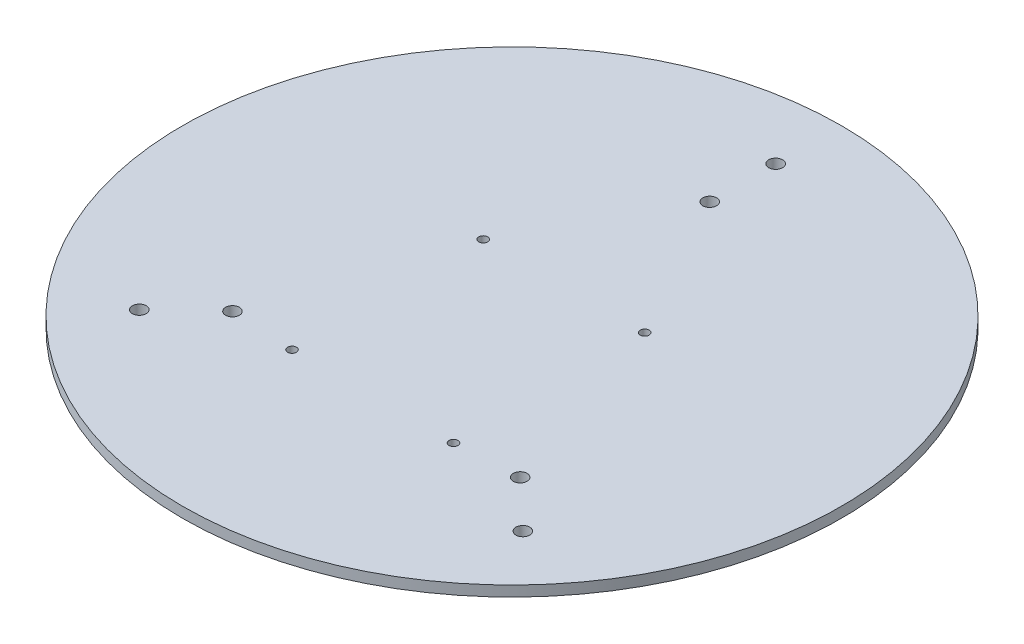
SolidWorks part; units mm, degrees
ref_plane "Front Plane" through (0, 0, 0) normal (0, 0, 1) x (1, 0, 0)
ref_plane "Top Plane" through (0, 0, 0) normal (0, 1, 0) x (1, 0, 0)
ref_plane "Right Plane" through (0, 0, 0) normal (1, 0, 0) x (0, 0, -1)
sketch "Sketch1" plane through (0, 0, 0) normal (0, 1, 0) x (1, 0, 0)
  line L0 (0, 100) -> (0, -100) construction
  line L1 (-24.5, 42.25) -> (24.5, 42.25) construction
  line L2 (-24.5, 42.25) -> (-24.5, -42.25) construction
  line L3 (-24.5, -42.25) -> (24.5, -42.25) construction
  line L4 (24.5, 42.25) -> (24.5, -42.25) construction
  line L5 (-24.5, 42.25) -> (24.5, -42.25) construction
  line L6 (-24.5, -42.25) -> (24.5, 42.25) construction
  line L7 (-24.5, -42.25) -> (24.5, -42.25) construction
  line L8 (-24.5, -42.25) -> (-24.5, 15.75) construction
  line L9 (-24.5, 15.75) -> (24.5, 15.75) construction
  line L10 (24.5, -42.25) -> (24.5, 15.75) construction
  line L11 (0, 0) -> (91.8216, 39.608) construction
  line L12 (0, 0) -> (-91.8216, 39.608) construction
  circle A0 centre (0, 0) radius 100
  circle A1 centre (-24.5, -42.25) radius 1.35
  circle A2 centre (24.5, -42.25) radius 1.35
  circle A3 centre (24.5, 15.75) radius 1.35
  circle A4 centre (-24.5, 15.75) radius 1.35
  circle A5 centre (0, 80) radius 2.1
  circle A6 centre (0, 60) radius 2.1
  circle A7 centre (43.6424, -41.1745) radius 2.1
  circle A8 centre (58.1899, -54.8993) radius 2.1
  circle A9 centre (-58.1899, -54.8993) radius 2.1
  circle A10 centre (-43.6424, -41.1745) radius 2.1
  dimension "D1" = 200
  dimension "D3" = 2.7
  dimension "D6" = 4.2
  dimension "D2" = 49
  dimension "D4" = 58
  dimension "D5" = 84.5
  dimension "D7" = 20
  dimension "D8" = 20
  dimension "D9" = 66.667
extrude "Boss-Extrude1" add sketch "Sketch1" along normal blind 3.175
